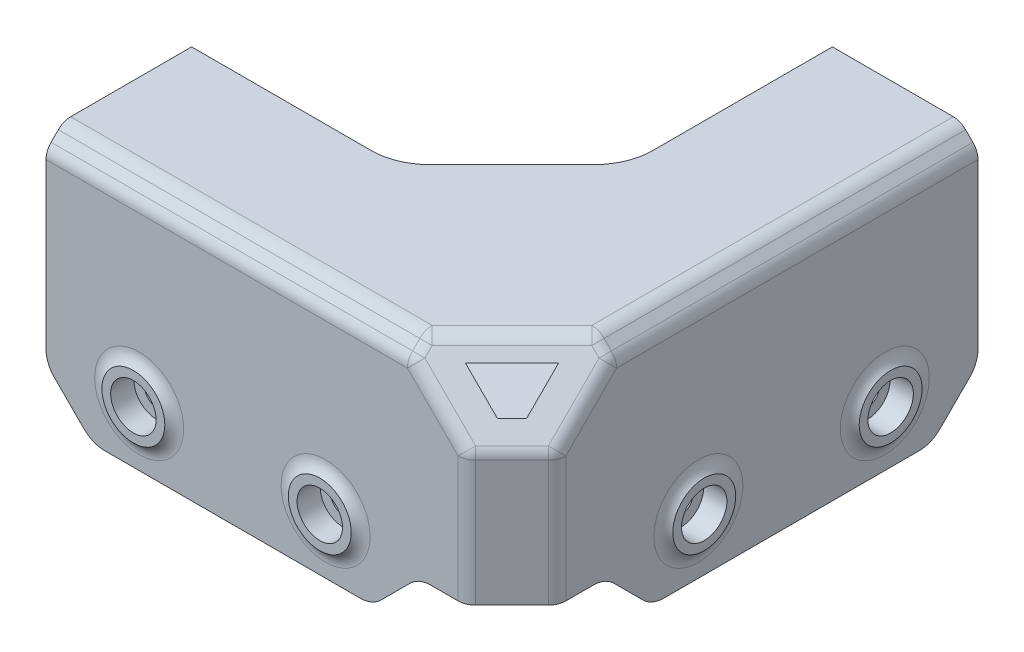
SolidWorks part; units mm, degrees
material "ABS"
ref_plane "Front Plane" through (0, 0, 0) normal (0, 0, 1) x (1, 0, 0)
ref_plane "Top Plane" through (0, 0, 0) normal (0, 1, 0) x (1, 0, 0)
ref_plane "Right Plane" through (0, 0, 0) normal (1, 0, 0) x (0, 0, -1)
sketch "Sketch1" plane through (0, 0, 0) normal (0, 1, 0) x (1, 0, 0)
  line L0 (0, 0) -> (-55, 0)
  line L1 (-55, 0) -> (-55, -25)
  line L2 (-55, -25) -> (25, -25)
  line L3 (25, -25) -> (25, 55)
  line L4 (25, 55) -> (0, 55)
  line L5 (0, 55) -> (0, 0)
  dimension "D1" = 80
  dimension "D2" = 25
extrude "Boss-Extrude1" add sketch "Sketch1" along normal blind 2
sketch "Sketch2" plane through (0, 0, 0) normal (0, -1, 0) x (1, 0, 0)
  line L0 (-55, 25) -> (25, 25)
  line L1 (25, 25) -> (25, -55)
  line L2 (25, -55) -> (20, -55)
  line L3 (25, -55) -> (0, -55) construction
  line L4 (20, -55) -> (20, 20)
  line L5 (20, 20) -> (-55, 20)
  line L6 (-55, 0) -> (-55, 25) construction
  line L7 (-55, 20) -> (-55, 25)
  dimension "D1" = 5
extrude "Boss-Extrude2" add sketch "Sketch2" along normal blind 20
ref_plane "Plane1" through (0, 0, 0) normal (-0.7071, 0, 0.7071) x (0.7071, 0, 0.7071)
sketch "Sketch4" plane through (-55, 0, 0) normal (-1, 0, 0) x (0, 0, 1)
  line L0 (25, 2) -> (25, 22.5)
  line L1 (25, 22.5) -> (0, 22.5)
  line L2 (0, 22.5) -> (0, 19.5)
  line L3 (0, 19.5) -> (20.5, 19.5)
  line L4 (20.5, 19.5) -> (20.5, 14)
  line L5 (20.5, 14) -> (0, 14)
  line L6 (0, 14) -> (0, 5.5)
  line L7 (0, 5.5) -> (20.5, 5.5)
  line L8 (20.5, 5.5) -> (20.5, 2)
  line L9 (0, 2) -> (25, 2) construction
  line L10 (20.5, 2) -> (25, 2)
  line L12 (0, 2) -> (0, 0) construction
  line L13 (20, -20) -> (20, 0) construction
  dimension "D1" = 3.5
  dimension "D2" = 5.5
  dimension "D3" = 8.5
  dimension "D4" = 3
  dimension "D5" = 0.5
extrude "Boss-Extrude3" add sketch "Sketch4" against normal up to surface (75.5 mm away) up to plane "Plane1"
mirror "Mirror1" about plane through (0, 0, 0) normal (-0.7071, 0, 0.7071) of "Boss-Extrude3"
chamfer "Chamfer1" distance 20 angle 45 3 edges at (0, 1, 0) (0, 9.75, 0) (0, 21, 0)
fillet "Fillet1" radius 10 6 edges at (0, 1, -20) (0, 9.75, -20) (0, 21, -20) (-20, 1, 0) (-20, 9.75, 0) (-20, 21, 0)
sketch "Sketch5" plane through (0, 0, 25) normal (0, 0, 1) x (1, 0, 0)
  line L0 (-55, -10) -> (-7, -10) construction
  line L1 (-55, 22.5) -> (-55, -20) construction
  line L2 (25, -20) -> (-55, -20) construction
  circle A0 centre (-39, -10) radius 2.1
  circle A1 centre (-7, -10) radius 2.1
  dimension "D1" = 4.2
  dimension "D2" = 16
  dimension "D3" = 32
  dimension "D4" = 10
extrude "Cut-Extrude1" cut sketch "Sketch5" against normal through all
mirror "Mirror2" about plane through (0, 0, 0) normal (-0.7071, 0, 0.7071) of "Cut-Extrude1"
sketch "Sketch6" plane through (0, 0, 25) normal (0, 0, 1) x (1, 0, 0)
  circle A0 centre (-39, -10) radius 3.9
  circle A1 centre (-7, -10) radius 3.9
  dimension "D1" = 7.8
extrude "Cut-Extrude2" cut sketch "Sketch6" against normal blind 3
sketch "Sketch7" plane through (0, 0, 25) normal (0, 0, 1) x (1, 0, 0)
  circle A0 centre (-7, -10) radius 3.9 construction
  circle A1 centre (-39, -10) radius 3.9 construction
  circle A2 centre (-7, -10) radius 3.9
  circle A3 centre (-39, -10) radius 3.9
  circle A4 centre (-39, -10) radius 5.4
  circle A5 centre (-7, -10) radius 5.4
  circle A6 centre (-39, -10) radius 3.9 construction
  dimension "D1" = 1.5
extrude "Boss-Extrude4" add sketch "Sketch7" along normal blind 1
mirror "Mirror4" about plane through (0, 0, 0) normal (-0.7071, 0, 0.7071) of "Boss-Extrude4"
sketch "Sketch8" plane through (0, 22.5, 0) normal (0, 1, 0) x (1, 0, 0)
  line L0 (5, -25) -> (25, -5)
  line L1 (25, -25) -> (-55, -25) construction
  line L2 (25, -25) -> (25, 55) construction
  line L3 (25, -5) -> (25, -25)
  line L4 (25, -25) -> (5, -25)
  dimension "D1" = 20
ref_plane "Plane2" through (0, 2.5, 0) normal (0, 1, 0) x (1, 0, 0)
sketch "Sketch9" plane through (0, 2.5, 0) normal (0, 1, 0) x (1, 0, 0)
  point P0 (25, -25)
loft "Cut-Loft1" cut profiles "Sketch9", "Sketch8"
chamfer "Chamfer4" distance 3 angle 45 2 edges
chamfer "Chamfer6" distance 8 angle 45 1 edges at (25, -8.75, 25)
fillet "Fillet4" radius 3 16 edges at (-23.5, 19.5, 25) (25, 19.5, -23.5) (25, -10, -33.6) (25, -10, -1.6) (-12.4, -10, 25) (-44.4, -10, 25) (21, 10.5, 21) (25, -4.75, 17) (17, -4.75, 25)
chamfer "Chamfer5" distance 8 angle 45 2 edges at (22.5, -20, -55) (-55, -20, 22.5)
sketch "Sketch10" plane through (0, 0, 25) normal (0, 0, 1) x (1, 0, 0)
  line L0 (1, -20) -> (9, -12)
  line L1 (15.7574, -20) -> (-47, -20) construction
  line L2 (9, -12) -> (25, -12)
  line L4 (25, -12) -> (25, -20)
  line L5 (25, -20) -> (1, -20)
  line L6 (-55, -12) -> (-47, -20) construction
  line L7 (-55, 18.2574) -> (-55, -12) construction
  dimension "D1" = 64
extrude "Cut-Extrude3" cut sketch "Sketch10" against normal blind 5
mirror "Mirror5" about plane through (0, 0, 0) normal (-0.7071, 0, 0.7071) of "Cut-Extrude3"
fillet "Fillet5" radius 5 8 edges at (22.5, -12, -55) (22.5, -20, -47) (22.5, -20, 1) (22.5, -12, 9) (9, -12, 22.5) (1, -20, 22.5) (-47, -20, 22.5) (-55, -12, 22.5)
sketch "Sketch11" plane through (25, 0, 0) normal (1, 0, 0) x (0, 0, -1)
  circle A0 centre (39, -10) radius 3.9 construction
  circle A1 centre (7, -10) radius 3.9
  circle A2 centre (7, -10) radius 3.9
  circle A3 centre (39, -10) radius 3.9
  dimension "D1" = 0
extrude "Cut-Extrude4" cut sketch "Sketch11" against normal blind 3
